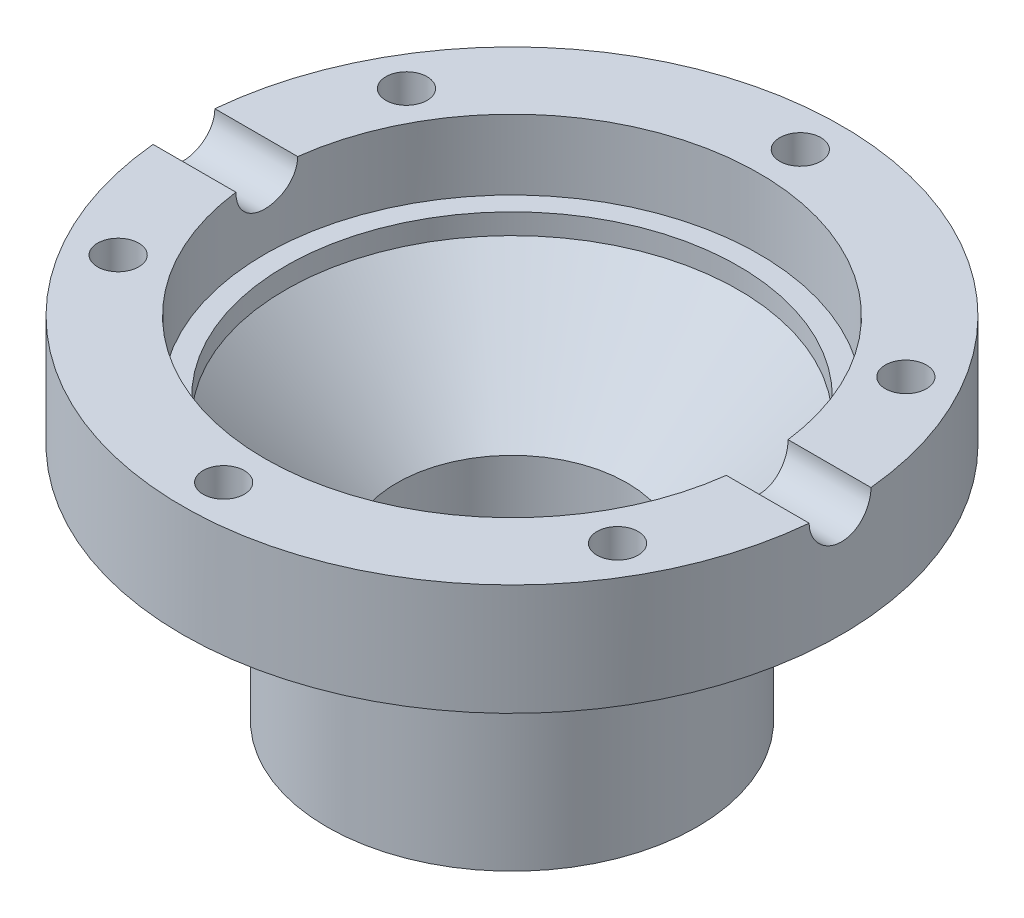
SolidWorks part; units mm, degrees
ref_plane "Front Plane" through (0, 0, 0) normal (0, 0, 1) x (1, 0, 0)
ref_plane "Top Plane" through (0, 0, 0) normal (0, 1, 0) x (1, 0, 0)
ref_plane "Right Plane" through (0, 0, 0) normal (1, 0, 0) x (0, 0, -1)
ref_axis "Centerline" through (0, 55, 0) along (0, -1, 0)
sketch "Sketch1" plane through (0, 0, 0) normal (0, 1, 0) x (1, 0, 0)
  circle A0 centre (0, 0) radius 20.32
  dimension "D1" = 40.64
extrude "Boss-Extrude1" add sketch "Sketch1" along normal blind 21.59
sketch "Sketch2" plane through (0, 0, 0) normal (0, 0, 1) x (1, 0, 0)
  line L0 (0, 26.2246) -> (0, -7.0612) construction
  line L5 (20.32, 21.59) -> (-20.32, 21.59) construction
  line L6 (0, 21.59) -> (-15.24, 21.59)
  line L7 (0, 21.59) -> (0, 17.272)
  line L8 (0, 17.272) -> (-15.24, 17.272)
  line L9 (-15.24, 21.59) -> (-15.24, 17.272)
  line L10 (-20.32, 21.59) -> (-20.32, 0) construction
  dimension "D1" = 5.08
  dimension "D2" = 4.318
revolve "Cut-Revolve1" cut sketch "Sketch2" angle 360 about axis through (0, 55, 0) along (0, -1, 0)
sketch "Sketch3" plane through (0, 0, 0) normal (0, 0, 1) x (1, 0, 0)
  line L0 (-20.32, 0) -> (20.32, 0) construction
  line L1 (-20.32, 14.732) -> (-15.24, 14.732)
  line L2 (-20.32, 14.732) -> (-20.32, 0)
  line L3 (-20.32, 0) -> (-15.24, 0)
  line L4 (-15.24, 14.732) -> (-15.24, 0)
  line L5 (20.32, 21.59) -> (-20.32, 21.59) construction
  line L6 (-20.32, 21.59) -> (-20.32, 0) construction
  dimension "D1" = 6.858
  dimension "D2" = 5.08
revolve "Cut-Revolve2" cut sketch "Sketch3" angle 360 about axis through (0, 55, 0) along (0, -1, 0)
sketch "Sketch4" plane through (0, 21.59, 0) normal (0, 1, 0) x (1, 0, 0)
  line L0 (0, 29.0947) -> (0, -35.1526) construction
  circle A0 centre (0, 17.78) radius 1.27
  dimension "D1" = 2.54
  dimension "D2" = 17.78
extrude "Cut-Extrude1" cut sketch "Sketch4" against normal up to next
pattern_circular "CirPattern1" count 6 over 360 about axis through (0, 55, 0) along (0, -1, 0) of "Cut-Extrude1"
sketch "Sketch5" plane through (0, 0, 0) normal (0, -1, 0) x (1, 0, 0)
  circle A0 centre (0, 0) radius 7.0968
  dimension "D1" = 14.1935
extrude "Cut-Extrude2" cut sketch "Sketch5" against normal up to next
sketch "Sketch7" plane through (0, 0, 0) normal (0, 0, 1) x (1, 0, 0)
  line L0 (-19.3213, 14.732) -> (23.1214, 14.732) construction
  line L1 (-20.32, 14.732) -> (20.32, 14.732) construction
  line L2 (-15.24, 14.732) -> (-15.24, 25.6293) construction
  line L4 (-15.24, 14.732) -> (-11.4097, 10.9017)
  line L5 (-11.4097, 10.9017) -> (-11.4097, 0)
  line L6 (-15.24, 0) -> (15.24, 0) construction
  line L7 (-11.4097, 0) -> (-15.24, 0)
  line L9 (-15.24, 14.732) -> (-15.24, 0)
  dimension "D1" = 45
  dimension "D2" = 10.9017
revolve "Cut-Revolve3" cut sketch "Sketch7" angle 360 about axis through (0, 55, 0) along (0, -1, 0)
sketch "Sketch8" plane through (0, 0, 0) normal (0, 0, 1) x (1, 0, 0)
  line L0 (-4.699, 24.8968) -> (-4.699, 18.7411) construction
  line L1 (-15.24, 24.5608) -> (-15.24, -3.2139) construction
  line L2 (15.24, 17.272) -> (-15.24, 17.272) construction
  line L3 (-4.699, 17.272) -> (-13.97, 17.272)
  line L4 (-13.97, 16.002) -> (-4.699, 6.731)
  line L5 (-22.2629, 0) -> (17.7783, 0) construction
  line L6 (-4.699, 6.731) -> (-4.699, 17.272)
  line L7 (-4.699, 17.272) -> (-4.699, -4.4972) construction
  line L8 (-13.97, 17.272) -> (-13.97, 16.002)
  line L9 (-13.97, 16.002) -> (-15.24, 17.272) construction
  line L10 (-15.24, 17.272) -> (-13.97, 17.272) construction
  dimension "D1" = 4.699
  dimension "D2" = 15.24
  dimension "D3" = 45
  dimension "D4" = 1.27
revolve "Cut-Revolve4" cut sketch "Sketch8" angle 360 about axis through (0, 55, 0) along (0, -1, 0)
ref_plane "Inlet Plane" through (20.32, 0, 0) normal (1, 0, 0) x (0, 0, -1)
sketch "Sketch9" plane through (20.32, 0, 0) normal (1, 0, 0) x (0, 0, -1)
  line L0 (0, 25.9244) -> (0, -6.8119) construction
  line L1 (20.32, 21.59) -> (-20.32, 21.59) construction
  circle A0 centre (0, 21.59) radius 1.905
  dimension "D1" = 3.81
extrude "Cut-Extrude3" cut sketch "Sketch9" against normal through all
